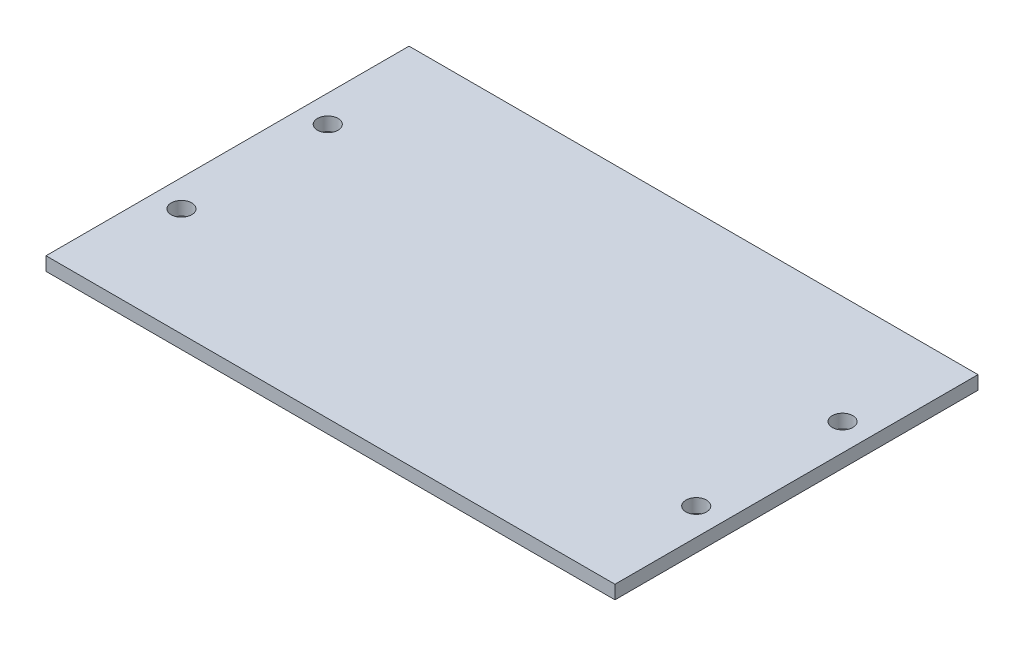
SolidWorks part; units mm, degrees
material "AISI Type A2 Tool Steel"
ref_plane "Front Plane" through (0, 0, 0) normal (0, 0, 1) x (1, 0, 0)
ref_plane "Top Plane" through (0, 0, 0) normal (0, 1, 0) x (1, 0, 0)
ref_plane "Right Plane" through (0, 0, 0) normal (1, 0, 0) x (0, 0, -1)
sketch "Sketch1" plane through (0, 0, 0) normal (0, 1, 0) x (1, 0, 0)
  line L1 (-45.1884, 47.6545) -> (88.1616, 47.6545)
  line L2 (-45.1884, 47.6545) -> (-45.1884, -37.4355)
  line L3 (-45.1884, -37.4355) -> (88.1616, -37.4355)
  line L4 (88.1616, 47.6545) -> (88.1616, -37.4355)
  dimension "D1" = 133.35
  dimension "D2" = 85.09
extrude "Boss-Extrude1" add sketch "Sketch1" along normal blind 3.175
sketch "Sketch2" plane through (0, 3.175, 0) normal (0, 1, 0) x (1, 0, 0)
  line L0 (88.1616, -37.4355) -> (88.1616, 47.6545) construction
  line L1 (-45.1884, -37.4355) -> (88.1616, -37.4355) construction
  line L3 (88.1616, 47.6545) -> (-45.1884, 47.6545) construction
  line L4 (-45.1884, 47.6545) -> (-45.1884, -37.4355) construction
  circle A0 centre (81.8116, -12.0355) radius 2.413
  circle A1 centre (81.8116, 22.2545) radius 2.413
  circle A2 centre (-38.8384, 22.2545) radius 2.413
  circle A3 centre (-38.8384, -12.0355) radius 2.413
  point P0 (81.8116, -12.0355)
  point P1 (-38.8384, -12.0355)
  point P2 (81.8116, 22.2545)
  point P9 (-38.8384, 22.2545)
  dimension "D5" = 4.826
  dimension "D1" = 6.35
  dimension "D2" = 6.35
  dimension "D3" = 25.4
  dimension "D4" = 25.4
extrude "Cut-Extrude1" cut sketch "Sketch2" against normal through all
